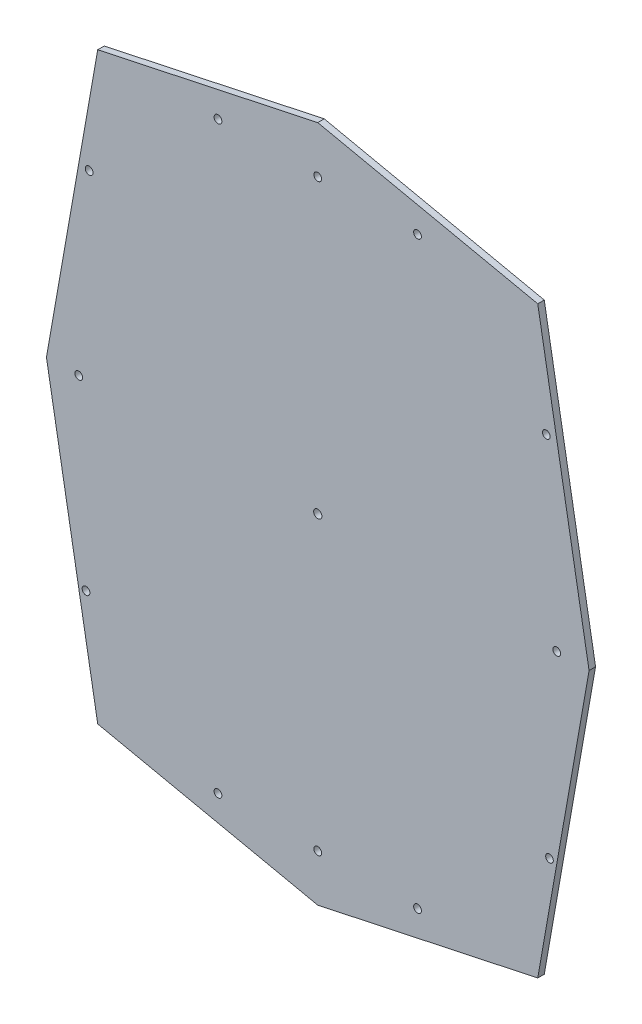
SolidWorks part; units mm, degrees
ref_plane "Front Plane" through (0, 0, 0) normal (0, 0, 1) x (1, 0, 0)
ref_plane "Top Plane" through (0, 0, 0) normal (0, 1, 0) x (1, 0, 0)
ref_plane "Right Plane" through (0, 0, 0) normal (1, 0, 0) x (0, 0, -1)
sketch "Sketch1" plane through (0, 0, 6.35) normal (0, 0, 1) x (1, 0, 0)
  line L0 (-107.5, 142.6399) -> (-132.5632, 0)
  line L10 (-107.5, -142.6399) -> (-132.5632, 0)
  line L13 (0, 188.5) -> (0, 142.6399) construction
  line L14 (-130, 89.4108) -> (-111.25, 89.4108) construction
  line L15 (-141, 0) -> (-116.7559, 0) construction
  line L18 (107.5, -142.6399) -> (132.5632, 0)
  line L19 (107.5, 142.6399) -> (132.5632, 0)
  line L24 (-107.5, 142.6399) -> (0, 165.5699)
  line L25 (0, 165.5699) -> (107.5, 142.6399)
  line L27 (-184.8413, 0) -> (193.3832, 0) construction
  line L33 (0, -165.5699) -> (107.5, -142.6399)
  line L34 (-107.5, -142.6399) -> (0, -165.5699)
  circle A25 centre (48.75, -142.6399) radius 1.8987
  circle A26 centre (0, -142.6399) radius 1.8987
  circle A27 centre (-48.75, -142.6399) radius 1.8987
  circle A28 centre (-113.2269, -89.1534) radius 1.8987
  circle A29 centre (-116.75, 0.1657) radius 1.8987
  circle A30 centre (-111.6902, 89.4108) radius 1.8987
  circle A31 centre (111.6902, 89.4108) radius 1.8987
  circle A32 centre (116.75, 0.1657) radius 1.8986
  circle A33 centre (113.2269, -89.1534) radius 1.8692
  circle A37 centre (48.75, 142.6399) radius 1.8987
  circle A38 centre (0, 142.6399) radius 1.8987
  circle A39 centre (-48.75, 142.6399) radius 1.8987
  point P0 (0, 0)
  point P16 (0, -142.6399)
  point P17 (0, 142.6399)
extrude "MainBody" add sketch "Sketch1" along normal blind 3.175
hole_wizard "#10-32 Tapped Hole1" positions "Sketch2" profile "Sketch3" tap size "#10-32" standard "ANSI Inch" end condition up to next
sketch "Sketch2" plane through (0, 0, 9.525) normal (0, 0, 1) x (1, 0, 0)
  point P0 (0, 0)
sketch "Sketch3" plane through (0, 0, 9.525) normal (1, 0, 0) x (0, -1, 0)
  line L0 (0, 0) -> (0, 3.175)
  line L1 (0, 3.175) -> (2.0193, 3.175)
  line L2 (2.0193, 3.175) -> (2.0193, 0)
  line L5 (2.0193, 0) -> (0, 0)
  line L11 (0, -6.35) -> (0, 107.95) construction
  dimension "Thru Tap Drill Dia." = 4.0386
  dimension "Thru Tap Drill Depth" = 3.175
cosmetic thread "Hole Thread1" parameters "D2"=4.826
